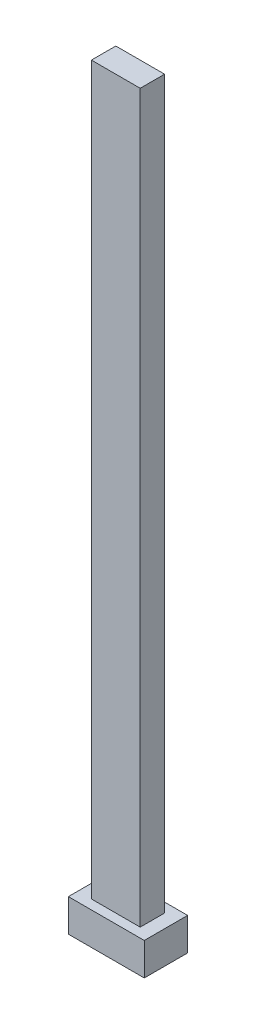
SolidWorks part; units mm, degrees
ref_plane "Front Plane" through (0, 0, 0) normal (0, 0, 1) x (1, 0, 0)
ref_plane "Top Plane" through (0, 0, 0) normal (0, 1, 0) x (1, 0, 0)
ref_plane "Right Plane" through (0, 0, 0) normal (1, 0, 0) x (0, 0, -1)
sketch "Sketch1" plane through (0, 0, 0) normal (0, 1, 0) x (1, 0, 0)
  line L1 (3.5, 2) -> (-3.5, 2)
  line L2 (3.5, 2) -> (3.5, -2)
  line L3 (3.5, -2) -> (-3.5, -2)
  line L4 (-3.5, 2) -> (-3.5, -2)
  line L5 (3.5, 2) -> (-3.5, -2) construction
  line L6 (3.5, -2) -> (-3.5, 2) construction
  line L7 (2.25, 1.125) -> (-2.25, 1.125)
  line L8 (2.25, 1.125) -> (2.25, -1.125)
  line L9 (2.25, -1.125) -> (-2.25, -1.125)
  line L10 (-2.25, 1.125) -> (-2.25, -1.125)
  line L11 (2.25, 1.125) -> (-2.25, -1.125) construction
  line L12 (2.25, -1.125) -> (-2.25, 1.125) construction
  point P0 (0, 0)
  point P6 (0, 0)
  dimension "D1" = 4
  dimension "D2" = 7
  dimension "D3" = 4.5
  dimension "D4" = 2.25
extrude "Boss-Extrude1" add sketch "Sketch1" along normal blind 3
extrude "Boss-Extrude2" add sketch "Sketch1<2>" along normal blind 70 contours L7 L10 L9 L8 region at (0, 0, 0)
sketch "Sketch1<2>" plane through (0, 0, 0) normal (0, 1, 0) x (1, 0, 0) same geometry as "Sketch1"
